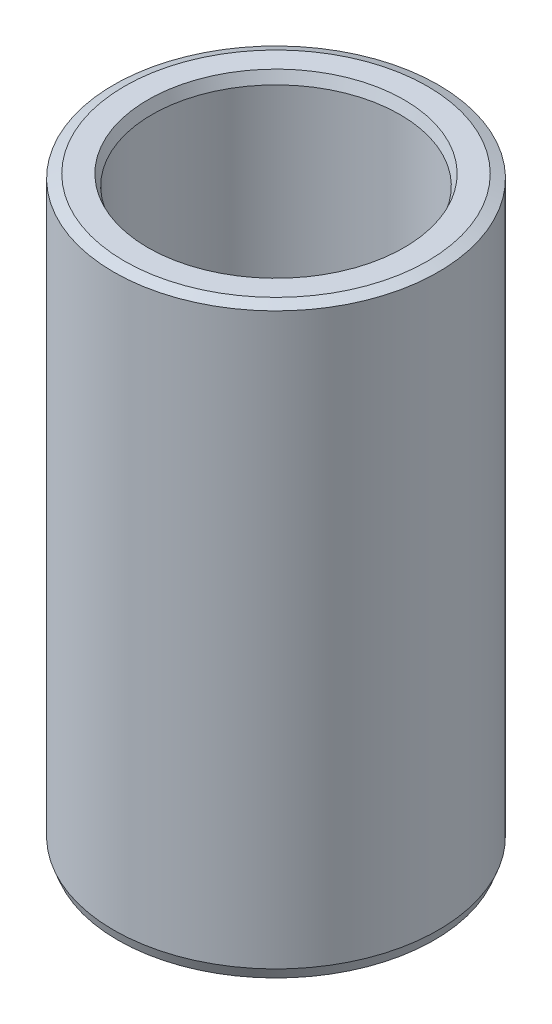
SolidWorks part; units mm, degrees
ref_plane "Front Plane" through (0, 0, 0) normal (0, 0, 1) x (1, 0, 0)
ref_plane "Top Plane" through (0, 0, 0) normal (0, 1, 0) x (1, 0, 0)
ref_plane "Right Plane" through (0, 0, 0) normal (1, 0, 0) x (0, 0, -1)
sketch "Sketch1" plane through (0, 0, 0) normal (0, 1, 0) x (1, 0, 0)
  circle A0 centre (0, 0) radius 32.5
  dimension "SLEEVE_OD" = 65
extrude "Boss-Extrude1" add sketch "Sketch1" along normal blind 117.1283
sketch "Sketch2" plane through (0, 0, 0) normal (0, 1, 0) x (1, 0, 0)
  circle A0 centre (0, 0) radius 24.8371
  dimension "BORE_D" = 49.6741
extrude "Cut-Extrude1" cut sketch "Sketch2" along normal through all
chamfer "Chamfer1" distance 0.8243 angle 69.035 4 edges at (0, 117.1283, 24.8371) (0, 0, 24.8371) (0, 0, 32.5) (0, 117.1283, 32.5) first distance on face at (0, 117.1283, 24.8371) first distance on face at (0, 0, 24.8371) first distance on face at (0, 117.1283, 32.5)
